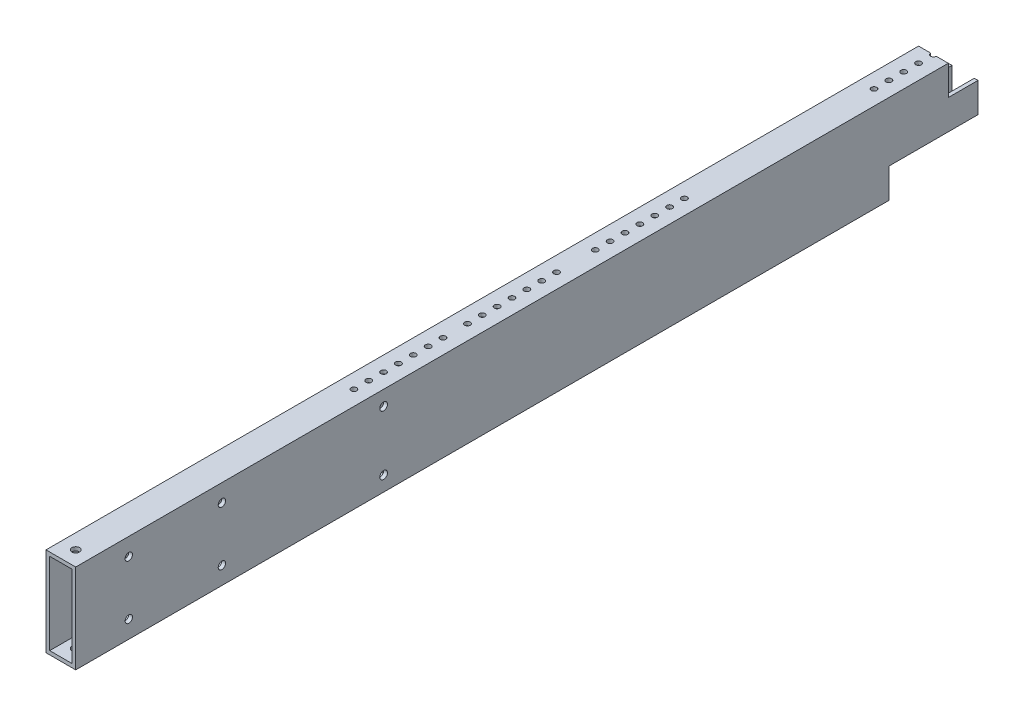
SolidWorks part; units mm, degrees
ref_plane "Front Plane" through (0, 0, 0) normal (0, 0, 1) x (1, 0, 0)
ref_plane "Top Plane" through (0, 0, 0) normal (0, 1, 0) x (1, 0, 0)
ref_plane "Right Plane" through (0, 0, 0) normal (1, 0, 0) x (0, 0, -1)
sketch "Sketch1" plane through (0, 0, 0) normal (0, 0, 1) x (1, 0, 0)
  line L1 (-12.7, -38.1) -> (12.7, -38.1)
  line L2 (-12.7, -38.1) -> (-12.7, 38.1)
  line L3 (-12.7, 38.1) -> (12.7, 38.1)
  line L4 (12.7, -38.1) -> (12.7, 38.1)
  line L5 (-12.7, -38.1) -> (12.7, 38.1) construction
  line L6 (-12.7, 38.1) -> (12.7, -38.1) construction
  point P0 (0, 0)
  dimension "D1" = 25.4
  dimension "D2" = 76.2
extrude "Boss-Extrude1" add sketch "Sketch1" along normal mid plane 771.398
shell "Shell1" thickness 3.175 removed face at (0, 0, -385.699) removed face at (0, 0, 385.699)
sketch "Sketch2" plane through (12.7, 0, 0) normal (1, 0, 0) x (0, 0, -1)
  line L1 (385.699, -38.1) -> (309.499, -38.1)
  line L2 (385.699, -38.1) -> (385.699, -12.7)
  line L3 (385.699, -12.7) -> (309.499, -12.7)
  line L4 (309.499, -38.1) -> (309.499, -12.7)
  dimension "D1" = 25.4
  dimension "D2" = 76.2
extrude "Cut-Extrude1" cut sketch "Sketch2" against normal through all
sketch "Sketch3" plane through (12.7, 0, 0) normal (1, 0, 0) x (0, 0, -1)
  line L1 (385.699, 38.1) -> (360.299, 38.1)
  line L2 (385.699, 38.1) -> (385.699, 12.7)
  line L3 (385.699, 12.7) -> (360.299, 12.7)
  line L4 (360.299, 38.1) -> (360.299, 12.7)
  dimension "D1" = 25.4
extrude "Cut-Extrude2" cut sketch "Sketch3" against normal through all
sketch "Sketch4" plane through (0, 38.1, 0) normal (0, 1, 0) x (1, 0, 0)
  line L0 (-12.7, 360.299) -> (12.7, 360.299) construction
  circle A0 centre (0, 147.3945) radius 2.3812
  circle A1 centre (0, 134.6945) radius 2.3812
  circle A2 centre (0, 121.9945) radius 2.3812
  circle A3 centre (0, 109.2945) radius 2.3812
  circle A4 centre (0, 96.5945) radius 2.3812
  circle A5 centre (0, 83.8945) radius 2.3812
  circle A6 centre (0, 71.1945) radius 2.3812
  circle A7 centre (0, 38.0987) radius 2.3812
  circle A8 centre (0, 25.3987) radius 2.3813
  circle A9 centre (0, 12.6987) radius 2.3813
  circle A10 centre (0, -0.0013) radius 2.3813
  circle A11 centre (0, -12.7013) radius 2.3812
  circle A12 centre (0, -25.4013) radius 2.3812
  circle A13 centre (0, -38.1013) radius 2.3812
  circle A15 centre (0, -58.9932) radius 2.3812
  circle A16 centre (0, -71.6932) radius 2.3812
  circle A17 centre (0, -84.3932) radius 2.3812
  circle A18 centre (0, -97.0932) radius 2.3812
  circle A19 centre (0, -109.7932) radius 2.3812
  circle A20 centre (0, -122.4932) radius 2.3812
  circle A21 centre (0, -135.1932) radius 2.3813
  point P33 (0, 360.299)
  dimension "D1" = 4.7625
  dimension "D3" = 12.7
  dimension "D4" = 12.7
  dimension "D5" = 12.7
  dimension "D6" = 12.7
  dimension "D7" = 12.7
  dimension "D8" = 12.7
  dimension "D9" = 322.2003
  dimension "D10" = 12.7
  dimension "D11" = 12.7
  dimension "D12" = 12.7
  dimension "D13" = 12.7
  dimension "D14" = 12.7
  dimension "D15" = 12.7
  dimension "D16" = 12.7
  dimension "D17" = 419.2922
  dimension "D18" = 12.7
  dimension "D19" = 12.7
  dimension "D20" = 12.7
  dimension "D21" = 12.7
  dimension "D22" = 12.7
  dimension "D2" = 212.9045
extrude "Cut-Extrude3" cut sketch "Sketch4" against normal through all
sketch "Sketch5" plane through (0, 38.1, 0) normal (0, 1, 0) x (1, 0, 0)
  line L0 (-12.7, 360.299) -> (12.7, 360.299) construction
  circle A0 centre (0, 360.299) radius 2.3813
  circle A1 centre (0, 347.599) radius 2.3813
  circle A2 centre (0, 334.899) radius 2.3813
  circle A3 centre (0, 322.199) radius 2.3813
  circle A4 centre (0, 309.499) radius 2.3813
  dimension "D1" = 4.7625
  dimension "D3" = 12.7
  dimension "D4" = 12.7
  dimension "D5" = 12.7
  dimension "D8" = 0
  dimension "D2" = 12.7
extrude "Cut-Extrude4" cut sketch "Sketch5" against normal up to next
sketch "Sketch6" plane through (0, -38.1, 0) normal (0, -1, 0) x (1, 0, 0)
  line L0 (-12.7, -309.499) -> (12.7, -309.499) construction
  circle A0 centre (0, -309.499) radius 2.3813
  circle A1 centre (0, -296.799) radius 2.3813
  circle A2 centre (0, -284.099) radius 2.3813
  circle A3 centre (0, -258.699) radius 2.3813
  circle A6 centre (0, -271.399) radius 2.3813
  dimension "D1" = 4.7625
  dimension "D2" = 12.7
  dimension "D3" = 12.7
  dimension "D4" = 12.7
  dimension "D5" = 12.7
  dimension "D6" = 0
extrude "Cut-Extrude5" cut sketch "Sketch6" against normal up to next
sketch3d "3DSketch1" [suppressed]
  line L0 (0, 34.925, -109.2945) -> (0, 38.1, -109.2945) construction
  line L1 (0, 34.925, 97.0932) -> (0, 38.1, 97.0932) construction
  point P0 (0, 38.1, -109.2945)
  point P1 (0, 0, 0)
  point P4 (0, 38.1, 97.0932)
sketch "Sketch11" plane through (12.7, 0, 0) normal (1, 0, 0) x (0, 0, -1)
  point P0 (-340.3244, 23.1254)
  point P1 (-260.7244, 23.1254)
  point P3 (-260.7244, -23.1)
  point P5 (-340.3244, -23.1)
hole_wizard "CBORE for M6 Hex Head Bolt1" positions "Sketch19" profile "Sketch18" counterbore size "M6" standard "Lanco STD" end condition through all
sketch "Sketch19" plane through (-12.7, 0, 0) normal (-1, 0, 0) x (0, 0, 1)
  point P0 (260.7244, 23.1254)
  point P3 (260.7244, -23.1)
  point P6 (340.3244, 23.1254)
  point P9 (340.3244, -23.1)
sketch "Sketch18" plane through (-12.7, 23.1254, 260.7244) normal (0, 1, 0) x (0, 0, 1)
  line L0 (0, 0) -> (0, 25.4)
  line L1 (0, 25.4) -> (3.15, 25.4)
  line L3 (3.15, 25.4) -> (3.15, 4)
  line L4 (3.15, 4) -> (7.2735, 4)
  line L5 (7.2735, 4) -> (7.2735, 0)
  line L7 (7.2735, 0) -> (0, 0)
  line L11 (0, -6.35) -> (0, 107.95) construction
  dimension "Thru Hole Dia." = 6.3
  dimension "Thru Hole Depth" = 25.4
  dimension "C'Bore Dia." = 14.547
  dimension "C'Bore Depth" = 4
hole_wizard "M6 Clearance Hole1" positions "Sketch21" profile "Sketch20" hole size "M6" standard "ANSI Metric" end condition through all
sketch "Sketch21" plane through (-12.7, 0, 0) normal (-1, 0, 0) x (0, 0, 1)
  line L0 (385.699, 38.1) -> (-360.299, 38.1) construction
  line L1 (385.699, 38.1) -> (385.699, -38.1) construction
  point P0 (122.4678, 25.4)
  point P2 (122.4678, -25.4)
  dimension "D1" = 12.7
  dimension "D2" = 63.5
  dimension "D3" = 263.2312
  dimension "D4" = 263.2312
sketch "Sketch20" plane through (-12.7, 25.4, 122.4678) normal (0, 1, 0) x (0, 0, 1)
  line L0 (0, 0) -> (0, 25.4)
  line L1 (0, 25.4) -> (3.3, 25.4)
  line L2 (3.3, 25.4) -> (3.3, 0)
  line L5 (3.3, 0) -> (0, 0)
  line L11 (0, -6.35) -> (0, 107.95) construction
  dimension "Thru Hole Dia." = 6.6
  dimension "Thru Hole Depth" = 25.4
hole_wizard "M6 Clearance Hole2" positions "Sketch23" profile "Sketch22" hole size "M6" standard "ANSI Metric" end condition through all
sketch "Sketch23" plane through (0, -38.1, 0) normal (0, -1, 0) x (-1, 0, 0)
  line L0 (12.7, -385.699) -> (-12.7, -385.699) construction
  line L1 (-12.7, -385.699) -> (-12.7, 309.499) construction
  point P0 (0, -372.999)
  dimension "D1" = 12.7
  dimension "D2" = 12.7
sketch "Sketch22" plane through (0, -38.1, 372.999) normal (1, 0, 0) x (0, 0, -1)
  line L0 (0, 0) -> (0, 76.2)
  line L1 (0, 76.2) -> (3.3, 76.2)
  line L2 (3.3, 76.2) -> (3.3, 0)
  line L5 (3.3, 0) -> (0, 0)
  line L11 (0, -6.35) -> (0, 107.95) construction
  dimension "Thru Hole Dia." = 6.6
  dimension "Thru Hole Depth" = 76.2
